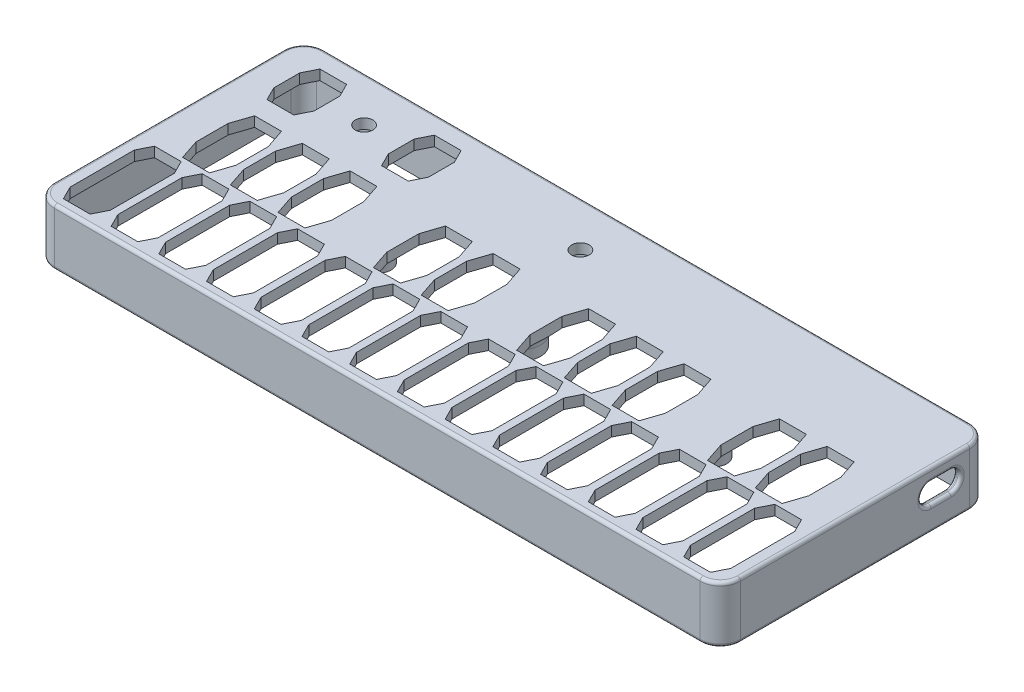
SolidWorks part; units mm, degrees
ref_plane "Front Plane" through (0, 0, 0) normal (0, 0, 1) x (1, 0, 0)
ref_plane "Top Plane" through (0, 0, 0) normal (0, 1, 0) x (1, 0, 0)
ref_plane "Right Plane" through (0, 0, 0) normal (1, 0, 0) x (0, 0, -1)
sketch "Sketch1" plane through (0, 0, 0) normal (0, 1, 0) x (1, 0, 0)
  line L1 (-133.985, 50.8) -> (133.985, 50.8)
  line L2 (-133.985, 50.8) -> (-133.985, -50.8)
  line L3 (-133.985, -50.8) -> (133.985, -50.8)
  line L4 (133.985, 50.8) -> (133.985, -50.8)
  line L5 (-133.985, 50.8) -> (133.985, -50.8) construction
  line L6 (-133.985, -50.8) -> (133.985, 50.8) construction
  point P0 (0, 0)
  dimension "D1" = 101.6
  dimension "D2" = 267.97
extrude "Boss-Extrude1" add sketch "Sketch1" along normal blind 4
extrude "Cut-Extrude2" cut sketch "Sketch3" against normal blind 4
sketch "Sketch3" plane through (-72.6823, 4, -171.6772) normal (0, 1, 0) x (1, 0, 0)
  line L0 (-14.5502, -162.7227) -> (-17.2012, -154.7696)
  line L1 (-17.2012, -154.7696) -> (-27.9343, -154.7696)
  line L2 (-27.9343, -154.7696) -> (-30.5853, -162.7227)
  line L3 (-30.5853, -162.7227) -> (-30.5853, -175.5517)
  line L4 (-30.5853, -175.5517) -> (-27.9343, -183.5048)
  line L5 (-27.9343, -183.5048) -> (-17.2012, -183.5048)
  line L6 (-17.2012, -183.5048) -> (-14.5502, -175.5517)
  line L7 (-14.5502, -175.5517) -> (-14.5502, -162.7227)
  line L8 (-24.0752, -190.6334) -> (-26.767, -185.2496)
  line L9 (-24.0752, -216.2211) -> (-24.0752, -190.6334)
  line L10 (-26.767, -221.6048) -> (-24.0752, -216.2211)
  line L11 (-37.4185, -221.6048) -> (-26.767, -221.6048)
  line L12 (-40.1103, -216.2211) -> (-37.4185, -221.6048)
  line L13 (-40.1103, -190.6334) -> (-40.1103, -216.2211)
  line L14 (-37.4185, -185.2496) -> (-40.1103, -190.6334)
  line L15 (-26.767, -185.2496) -> (-37.4185, -185.2496)
  line L24 (-59.1603, -190.6334) -> (-59.1603, -216.2211)
  line L25 (-59.1603, -216.2211) -> (-56.4685, -221.6048)
  line L26 (-56.4685, -221.6048) -> (-45.817, -221.6048)
  line L27 (-45.817, -221.6048) -> (-43.1252, -216.2211)
  line L28 (-43.1252, -216.2211) -> (-43.1252, -190.6334)
  line L29 (-43.1252, -190.6334) -> (-45.817, -185.2496)
  line L30 (-45.817, -185.2496) -> (-56.4685, -185.2496)
  line L31 (-56.4685, -185.2496) -> (-59.1603, -190.6334)
  line L32 (-5.0252, -190.6334) -> (-7.717, -185.2496)
  line L33 (-5.0252, -216.2211) -> (-5.0252, -190.6334)
  line L34 (-7.717, -221.6048) -> (-5.0252, -216.2211)
  line L35 (-18.3685, -221.6048) -> (-7.717, -221.6048)
  line L36 (-21.0603, -216.2211) -> (-18.3685, -221.6048)
  line L37 (-21.0603, -190.6334) -> (-21.0603, -216.2211)
  line L38 (-18.3685, -185.2496) -> (-21.0603, -190.6334)
  line L39 (-7.717, -185.2496) -> (-18.3685, -185.2496)
  line L40 (14.0248, -190.6334) -> (11.333, -185.2496)
  line L41 (14.0248, -216.2211) -> (14.0248, -190.6334)
  line L42 (11.333, -221.6048) -> (14.0248, -216.2211)
  line L43 (0.6815, -221.6048) -> (11.333, -221.6048)
  line L44 (-2.0103, -216.2211) -> (0.6815, -221.6048)
  line L45 (-2.0103, -190.6334) -> (-2.0103, -216.2211)
  line L46 (0.6815, -185.2496) -> (-2.0103, -190.6334)
  line L47 (11.333, -185.2496) -> (0.6815, -185.2496)
  line L48 (33.0748, -190.6334) -> (30.383, -185.2496)
  line L49 (33.0748, -216.2211) -> (33.0748, -190.6334)
  line L50 (30.383, -221.6048) -> (33.0748, -216.2211)
  line L51 (19.7315, -221.6048) -> (30.383, -221.6048)
  line L52 (17.0397, -216.2211) -> (19.7315, -221.6048)
  line L53 (17.0397, -190.6334) -> (17.0397, -216.2211)
  line L54 (19.7315, -185.2496) -> (17.0397, -190.6334)
  line L55 (30.383, -185.2496) -> (19.7315, -185.2496)
  line L56 (52.1248, -190.6334) -> (49.433, -185.2496)
  line L57 (52.1248, -216.2211) -> (52.1248, -190.6334)
  line L58 (49.433, -221.6048) -> (52.1248, -216.2211)
  line L59 (38.7815, -221.6048) -> (49.433, -221.6048)
  line L60 (36.0897, -216.2211) -> (38.7815, -221.6048)
  line L61 (36.0897, -190.6334) -> (36.0897, -216.2211)
  line L62 (38.7815, -185.2496) -> (36.0897, -190.6334)
  line L63 (49.433, -185.2496) -> (38.7815, -185.2496)
  line L64 (71.1748, -190.6334) -> (68.483, -185.2496)
  line L65 (71.1748, -216.2211) -> (71.1748, -190.6334)
  line L66 (68.483, -221.6048) -> (71.1748, -216.2211)
  line L67 (57.8315, -221.6048) -> (68.483, -221.6048)
  line L68 (55.1397, -216.2211) -> (57.8315, -221.6048)
  line L69 (55.1397, -190.6334) -> (55.1397, -216.2211)
  line L70 (57.8315, -185.2496) -> (55.1397, -190.6334)
  line L71 (68.483, -185.2496) -> (57.8315, -185.2496)
  line L72 (90.2248, -190.6334) -> (87.533, -185.2496)
  line L73 (90.2248, -216.2211) -> (90.2248, -190.6334)
  line L74 (87.533, -221.6048) -> (90.2248, -216.2211)
  line L75 (76.8815, -221.6048) -> (87.533, -221.6048)
  line L76 (74.1897, -216.2211) -> (76.8815, -221.6048)
  line L77 (74.1897, -190.6334) -> (74.1897, -216.2211)
  line L78 (76.8815, -185.2496) -> (74.1897, -190.6334)
  line L79 (87.533, -185.2496) -> (76.8815, -185.2496)
  line L80 (109.2748, -190.6334) -> (106.583, -185.2496)
  line L81 (109.2748, -216.2211) -> (109.2748, -190.6334)
  line L82 (106.583, -221.6048) -> (109.2748, -216.2211)
  line L83 (95.9315, -221.6048) -> (106.583, -221.6048)
  line L84 (93.2397, -216.2211) -> (95.9315, -221.6048)
  line L85 (93.2397, -190.6334) -> (93.2397, -216.2211)
  line L86 (95.9315, -185.2496) -> (93.2397, -190.6334)
  line L87 (106.583, -185.2496) -> (95.9315, -185.2496)
  line L88 (128.3248, -190.6334) -> (125.633, -185.2496)
  line L89 (128.3248, -216.2211) -> (128.3248, -190.6334)
  line L90 (125.633, -221.6048) -> (128.3248, -216.2211)
  line L91 (114.9815, -221.6048) -> (125.633, -221.6048)
  line L92 (112.2897, -216.2211) -> (114.9815, -221.6048)
  line L93 (112.2897, -190.6334) -> (112.2897, -216.2211)
  line L94 (114.9815, -185.2496) -> (112.2897, -190.6334)
  line L95 (125.633, -185.2496) -> (114.9815, -185.2496)
  line L96 (147.3748, -190.6334) -> (144.683, -185.2496)
  line L97 (147.3748, -216.2211) -> (147.3748, -190.6334)
  line L98 (144.683, -221.6048) -> (147.3748, -216.2211)
  line L99 (134.0315, -221.6048) -> (144.683, -221.6048)
  line L100 (131.3397, -216.2211) -> (134.0315, -221.6048)
  line L101 (131.3397, -190.6334) -> (131.3397, -216.2211)
  line L102 (134.0315, -185.2496) -> (131.3397, -190.6334)
  line L103 (144.683, -185.2496) -> (134.0315, -185.2496)
  line L104 (166.4248, -190.6334) -> (163.733, -185.2496)
  line L105 (166.4248, -216.2211) -> (166.4248, -190.6334)
  line L106 (163.733, -221.6048) -> (166.4248, -216.2211)
  line L107 (153.0815, -221.6048) -> (163.733, -221.6048)
  line L108 (150.3897, -216.2211) -> (153.0815, -221.6048)
  line L109 (150.3897, -190.6334) -> (150.3897, -216.2211)
  line L110 (153.0815, -185.2496) -> (150.3897, -190.6334)
  line L111 (163.733, -185.2496) -> (153.0815, -185.2496)
  line L112 (185.4748, -190.6334) -> (182.783, -185.2496)
  line L113 (185.4748, -216.2211) -> (185.4748, -190.6334)
  line L114 (182.783, -221.6048) -> (185.4748, -216.2211)
  line L115 (172.1315, -221.6048) -> (182.783, -221.6048)
  line L116 (169.4397, -216.2211) -> (172.1315, -221.6048)
  line L117 (169.4397, -190.6334) -> (169.4397, -216.2211)
  line L118 (172.1315, -185.2496) -> (169.4397, -190.6334)
  line L119 (182.783, -185.2496) -> (172.1315, -185.2496)
  line L120 (204.5248, -190.6334) -> (201.833, -185.2496)
  line L121 (204.5248, -216.2211) -> (204.5248, -190.6334)
  line L122 (201.833, -221.6048) -> (204.5248, -216.2211)
  line L123 (191.1815, -221.6048) -> (201.833, -221.6048)
  line L124 (188.4897, -216.2211) -> (191.1815, -221.6048)
  line L125 (188.4897, -190.6334) -> (188.4897, -216.2211)
  line L126 (191.1815, -185.2496) -> (188.4897, -190.6334)
  line L127 (201.833, -185.2496) -> (191.1815, -185.2496)
  line L144 (-33.6002, -175.5517) -> (-33.6002, -162.7227)
  line L145 (-33.6002, -162.7227) -> (-36.2512, -154.7696)
  line L146 (-36.2512, -154.7696) -> (-46.9843, -154.7696)
  line L147 (-46.9843, -154.7696) -> (-49.6353, -162.7227)
  line L148 (-49.6353, -162.7227) -> (-49.6353, -175.5517)
  line L149 (-49.6353, -175.5517) -> (-46.9843, -183.5048)
  line L150 (-46.9843, -183.5048) -> (-36.2512, -183.5048)
  line L151 (-36.2512, -183.5048) -> (-33.6002, -175.5517)
  line L160 (4.4998, -162.7227) -> (1.8488, -154.7696)
  line L161 (1.8488, -154.7696) -> (-8.8843, -154.7696)
  line L162 (-8.8843, -154.7696) -> (-11.5353, -162.7227)
  line L163 (-11.5353, -162.7227) -> (-11.5353, -175.5517)
  line L164 (-11.5353, -175.5517) -> (-8.8843, -183.5048)
  line L165 (-8.8843, -183.5048) -> (1.8488, -183.5048)
  line L166 (1.8488, -183.5048) -> (4.4998, -175.5517)
  line L167 (4.4998, -175.5517) -> (4.4998, -162.7227)
  line L216 (42.5998, -162.7227) -> (39.9488, -154.7696)
  line L217 (39.9488, -154.7696) -> (29.2157, -154.7696)
  line L218 (29.2157, -154.7696) -> (26.5647, -162.7227)
  line L219 (26.5647, -162.7227) -> (26.5647, -175.5517)
  line L220 (26.5647, -175.5517) -> (29.2157, -183.5048)
  line L221 (29.2157, -183.5048) -> (39.9488, -183.5048)
  line L222 (39.9488, -183.5048) -> (42.5998, -175.5517)
  line L223 (42.5998, -175.5517) -> (42.5998, -162.7227)
  line L240 (61.6498, -162.7227) -> (58.9988, -154.7696)
  line L241 (58.9988, -154.7696) -> (48.2657, -154.7696)
  line L242 (48.2657, -154.7696) -> (45.6147, -162.7227)
  line L243 (45.6147, -162.7227) -> (45.6147, -175.5517)
  line L244 (45.6147, -175.5517) -> (48.2657, -183.5048)
  line L245 (48.2657, -183.5048) -> (58.9988, -183.5048)
  line L246 (58.9988, -183.5048) -> (61.6498, -175.5517)
  line L247 (61.6498, -175.5517) -> (61.6498, -162.7227)
  line L256 (-36.7752, -141.2911) -> (-36.7752, -130.9434)
  line L257 (-36.7752, -130.9434) -> (-39.467, -125.5596)
  line L258 (-39.467, -125.5596) -> (-50.1185, -125.5596)
  line L259 (-50.1185, -125.5596) -> (-52.8103, -130.9434)
  line L260 (-52.8103, -130.9434) -> (-52.8103, -141.2911)
  line L261 (-52.8103, -141.2911) -> (-50.1185, -146.6748)
  line L262 (-50.1185, -146.6748) -> (-39.467, -146.6748)
  line L263 (-39.467, -146.6748) -> (-36.7752, -141.2911)
  line L280 (8.9448, -141.2911) -> (8.9448, -130.9434)
  line L281 (8.9448, -130.9434) -> (6.253, -125.5596)
  line L282 (6.253, -125.5596) -> (-4.3985, -125.5596)
  line L283 (-4.3985, -125.5596) -> (-7.0903, -130.9434)
  line L284 (-7.0903, -130.9434) -> (-7.0903, -141.2911)
  line L285 (-7.0903, -141.2911) -> (-4.3985, -146.6748)
  line L286 (-4.3985, -146.6748) -> (6.253, -146.6748)
  line L287 (6.253, -146.6748) -> (8.9448, -141.2911)
  line L288 (99.7498, -162.7227) -> (97.0988, -154.7696)
  line L289 (97.0988, -154.7696) -> (86.3657, -154.7696)
  line L290 (86.3657, -154.7696) -> (83.7147, -162.7227)
  line L291 (83.7147, -162.7227) -> (83.7147, -175.5517)
  line L292 (83.7147, -175.5517) -> (86.3657, -183.5048)
  line L293 (86.3657, -183.5048) -> (97.0988, -183.5048)
  line L294 (97.0988, -183.5048) -> (99.7498, -175.5517)
  line L295 (99.7498, -175.5517) -> (99.7498, -162.7227)
  line L296 (118.7998, -162.7227) -> (116.1488, -154.7696)
  line L297 (116.1488, -154.7696) -> (105.4157, -154.7696)
  line L298 (105.4157, -154.7696) -> (102.7647, -162.7227)
  line L299 (102.7647, -162.7227) -> (102.7647, -175.5517)
  line L300 (102.7647, -175.5517) -> (105.4157, -183.5048)
  line L301 (105.4157, -183.5048) -> (116.1488, -183.5048)
  line L302 (116.1488, -183.5048) -> (118.7998, -175.5517)
  line L303 (118.7998, -175.5517) -> (118.7998, -162.7227)
  line L304 (137.8498, -162.7227) -> (135.1988, -154.7696)
  line L305 (135.1988, -154.7696) -> (124.4657, -154.7696)
  line L306 (124.4657, -154.7696) -> (121.8147, -162.7227)
  line L307 (121.8147, -162.7227) -> (121.8147, -175.5517)
  line L308 (121.8147, -175.5517) -> (124.4657, -183.5048)
  line L309 (124.4657, -183.5048) -> (135.1988, -183.5048)
  line L310 (135.1988, -183.5048) -> (137.8498, -175.5517)
  line L311 (137.8498, -175.5517) -> (137.8498, -162.7227)
  line L320 (175.9498, -162.7227) -> (173.2988, -154.7696)
  line L321 (173.2988, -154.7696) -> (162.5657, -154.7696)
  line L322 (162.5657, -154.7696) -> (159.9147, -162.7227)
  line L323 (159.9147, -162.7227) -> (159.9147, -175.5517)
  line L324 (159.9147, -175.5517) -> (162.5657, -183.5048)
  line L325 (162.5657, -183.5048) -> (173.2988, -183.5048)
  line L326 (173.2988, -183.5048) -> (175.9498, -175.5517)
  line L327 (175.9498, -175.5517) -> (175.9498, -162.7227)
  line L328 (194.9998, -162.7227) -> (192.3488, -154.7696)
  line L329 (192.3488, -154.7696) -> (181.6157, -154.7696)
  line L330 (181.6157, -154.7696) -> (178.9647, -162.7227)
  line L331 (178.9647, -162.7227) -> (178.9647, -175.5517)
  line L332 (178.9647, -175.5517) -> (181.6157, -183.5048)
  line L333 (181.6157, -183.5048) -> (192.3488, -183.5048)
  line L334 (192.3488, -183.5048) -> (194.9998, -175.5517)
  line L335 (194.9998, -175.5517) -> (194.9998, -162.7227)
  line L364 (-61.3027, -125.9572) -> (-61.3027, -217.3972)
  line L365 (-61.3027, -217.3972) -> (-61.1296, -218.712)
  line L366 (-61.1296, -218.712) -> (-60.6222, -219.9372)
  line L367 (-60.6222, -219.9372) -> (-59.8148, -220.9893)
  line L368 (-59.8148, -220.9893) -> (-58.7627, -221.7966)
  line L369 (-58.7627, -221.7966) -> (-57.5375, -222.3041)
  line L370 (-57.5375, -222.3041) -> (-56.2227, -222.4772)
  line L371 (-56.2227, -222.4772) -> (201.5873, -222.4772)
  line L372 (201.5873, -222.4772) -> (202.9021, -222.3041)
  line L373 (202.9021, -222.3041) -> (204.1273, -221.7966)
  line L374 (204.1273, -221.7966) -> (205.1794, -220.9893)
  line L375 (205.1794, -220.9893) -> (205.9867, -219.9372)
  line L376 (205.9867, -219.9372) -> (206.4942, -218.712)
  line L377 (206.4942, -218.712) -> (206.6673, -217.3972)
  line L378 (206.6673, -217.3972) -> (206.6673, -125.9572)
  line L379 (206.6673, -125.9572) -> (206.4942, -124.6424)
  line L380 (206.4942, -124.6424) -> (205.9867, -123.4172)
  line L381 (205.9867, -123.4172) -> (205.1794, -122.3651)
  line L382 (205.1794, -122.3651) -> (204.1273, -121.5578)
  line L383 (204.1273, -121.5578) -> (202.9021, -121.0503)
  line L384 (202.9021, -121.0503) -> (201.5873, -120.8772)
  line L385 (201.5873, -120.8772) -> (-56.2227, -120.8772)
  line L386 (-56.2227, -120.8772) -> (-57.5375, -121.0503)
  line L387 (-57.5375, -121.0503) -> (-58.7627, -121.5578)
  line L388 (-58.7627, -121.5578) -> (-59.8148, -122.3651)
  line L389 (-59.8148, -122.3651) -> (-60.6222, -123.4172)
  line L390 (-60.6222, -123.4172) -> (-61.1296, -124.6424)
  line L391 (-61.1296, -124.6424) -> (-61.3027, -125.9572)
  circle A0 centre (64.4273, -136.1172) radius 3.5
  circle A1 centre (-21.9327, -136.1172) radius 3.5
fillet "Fillet1" radius 5.08 4 edges at (-133.985, 2, 50.8) (-133.985, 2, -50.8) (133.985, 2, -50.8) (133.985, 2, 50.8)
sketch "Sketch4" plane through (0, 0, 0) normal (0, -1, 0) x (-1, 0, 0)
  line L0 (128.905, -50.8) -> (-128.905, -50.8) construction
  line L1 (-133.985, -45.72) -> (-133.985, 45.72) construction
  line L2 (133.985, 45.72) -> (133.985, -45.72) construction
  circle A0 centre (-76.835, 3.81) radius 1.27
  circle A1 centre (57.15, 3.81) radius 1.27
  circle A2 centre (57.15, 3.81) radius 5.08
  circle A3 centre (-76.835, 3.81) radius 5.08
  circle A4 centre (0, 3.81) radius 7.62
  dimension "D1" = 54.61
  dimension "D5" = 2.54
  dimension "D6" = 2.54
  dimension "D7" = 10.16
  dimension "D8" = 10.16
  dimension "D9" = 15.24
  dimension "D2" = 54.61
  dimension "D3" = 57.15
  dimension "D4" = 76.835
  dimension "D10" = 54.61
  dimension "D11" = 57.15
extrude "Boss-Extrude2" add sketch "Sketch4" along normal blind 9
fillet "Fillet2" radius 5.08 3 edges at (76.835, 0, 1.27) (-57.15, 0, 1.27) (0, 0, 3.81)
sketch "Sketch5" plane through (0, 0, 0) normal (0, -1, 0) x (1, 0, 0)
  line L0 (128.905, -50.8) -> (-128.905, -50.8) construction
  line L1 (-133.985, -45.72) -> (-133.985, 45.72) construction
  line L2 (133.985, 45.72) -> (133.985, -45.72) construction
  circle A0 centre (-130.175, -46.99) radius 1.27
  circle A1 centre (130.175, -46.99) radius 1.27
  dimension "D3" = 2.54
  dimension "D5" = 3.81
  dimension "D6" = 2.54
  dimension "D1" = 3.81
  dimension "D2" = 3.81
  dimension "D4" = 3.81
sketch "Sketch6" plane through (0, 4, 0) normal (0, 1, 0) x (1, 0, 0)
  line L4 (-133.985, 45.72) -> (-133.985, -45.72)
  line L5 (-128.905, -50.8) -> (128.905, -50.8)
  line L6 (133.985, -45.72) -> (133.985, 45.72)
  line L7 (128.905, 50.8) -> (-128.905, 50.8)
  line L8 (-136.985, 45.72) -> (-136.985, -45.72)
  line L9 (-128.905, -53.8) -> (128.905, -53.8)
  line L10 (136.985, -45.72) -> (136.985, 45.72)
  line L11 (128.905, 53.8) -> (-128.905, 53.8)
  line L12 (-136.985, 45.72) -> (-136.985, -45.72)
  line L13 (-128.905, -53.8) -> (128.905, -53.8)
  line L14 (136.985, -45.72) -> (136.985, 45.72)
  line L15 (128.905, 53.8) -> (-128.905, 53.8)
  arc A4 (-133.985, -45.72) -> (-128.905, -50.8) centre (-128.905, -45.72) ccw
  arc A5 (128.905, -50.8) -> (133.985, -45.72) centre (128.905, -45.72) ccw
  arc A6 (133.985, 45.72) -> (128.905, 50.8) centre (128.905, 45.72) ccw
  arc A7 (-128.905, 50.8) -> (-133.985, 45.72) centre (-128.905, 45.72) ccw
  arc A8 (-136.985, -45.72) -> (-128.905, -53.8) centre (-128.905, -45.72) ccw
  arc A9 (128.905, -53.8) -> (136.985, -45.72) centre (128.905, -45.72) ccw
  arc A10 (136.985, 45.72) -> (128.905, 53.8) centre (128.905, 45.72) ccw
  arc A11 (-128.905, 53.8) -> (-136.985, 45.72) centre (-128.905, 45.72) ccw
  arc A12 (-136.985, -45.72) -> (-128.905, -53.8) centre (-128.905, -45.72) ccw
  arc A13 (128.905, -53.8) -> (136.985, -45.72) centre (128.905, -45.72) ccw
  arc A14 (136.985, 45.72) -> (128.905, 53.8) centre (128.905, 45.72) ccw
  arc A15 (-128.905, 53.8) -> (-136.985, 45.72) centre (-128.905, 45.72) ccw
  dimension "D1" = 3
  dimension "D2" = 3
extrude "Boss-Extrude3" add sketch "Sketch6" against normal blind 22.606
fillet "Fillet3" radius 1.27 16 edges at (-136.985, 4, 0) (-136.985, -18.606, 0) (-134.6184, 4, -51.4334) (-134.6184, -18.606, -51.4334) (0, 4, -53.8) (0, -18.606, -53.8) (134.6184, 4, -51.4334) (134.6184, -18.606, -51.4334) (136.985, 4, 0) (136.985, -18.606, 0) (134.6184, 4, 51.4334) (134.6184, -18.606, 51.4334) (0, 4, 53.8) (0, -18.606, 53.8) (-134.6184, 4, 51.4334) (-134.6184, -18.606, 51.4334)
sketch "Sketch7" plane through (133.985, 0, 0) normal (-1, 0, 0) x (0, 0, 1)
  line L0 (-38.29, -5) -> (-30.29, -5) construction
  line L1 (-38.29, -1) -> (-30.29, -1)
  line L2 (-38.29, -9) -> (-30.29, -9)
  line L4 (45.72, 0) -> (-45.72, 0) construction
  line L5 (-45.72, -18.606) -> (-45.72, 0) construction
  arc A0 (-38.29, -1) -> (-38.29, -9) centre (-38.29, -5) ccw
  arc A1 (-30.29, -9) -> (-30.29, -1) centre (-30.29, -5) ccw
  point P2 (-34.29, -5)
  point P9 (0, 0)
  point P10 (0, 0)
  dimension "D2" = 4
  dimension "D4" = 8
  dimension "D1" = 5
  dimension "D3" = 11.43
extrude "USB_Hole" cut sketch "Sketch7" against normal blind 22.606
fillet "Fillet4" radius 1.27 7 edges at (136.985, -1, -34.29) (136.985, -5, -42.29) (136.985, -9, -34.29) (133.985, -9, -34.29) (133.985, -5, -42.29) (136.985, -5, -26.29) (133.985, -5, -26.29)
